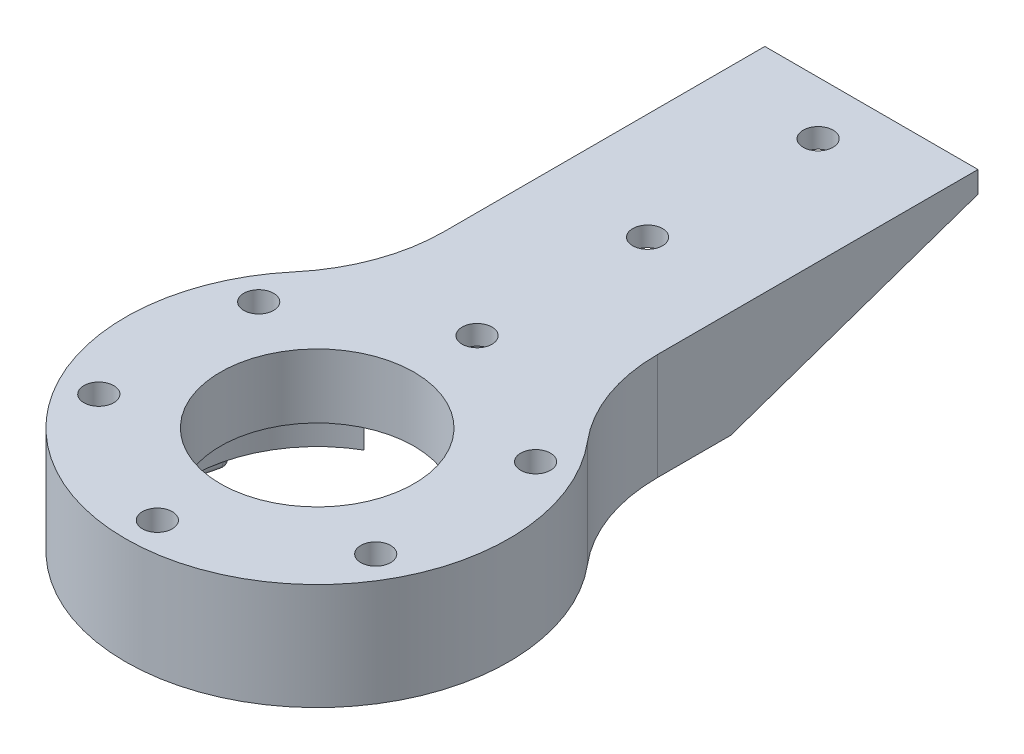
SolidWorks part; units mm, degrees
ref_plane "Front Plane" through (0, 0, 0) normal (0, 0, 1) x (1, 0, 0)
ref_plane "Top Plane" through (0, 0, 0) normal (0, 1, 0) x (1, 0, 0)
ref_plane "Right Plane" through (0, 0, 0) normal (1, 0, 0) x (0, 0, -1)
sketch "Sketch1" plane through (0, 0, 0) normal (0, 1, 0) x (1, 0, 0)
  line L0 (0, 82.55) -> (0, 0) construction
  line L1 (-15.875, 82.55) -> (15.875, 82.55)
  line L2 (-15.875, 82.55) -> (-15.875, 23.7595)
  line L4 (15.875, 82.55) -> (15.875, 23.7595)
  circle A0 centre (0, 0) radius 23.8125 construction
  arc A1 (-15.875, 23.7595) -> (15.875, 23.7595) centre (0, 0) ccw
  circle A2 centre (0, 0) radius 14.4145
  circle A3 centre (0, 23.8125) radius 2.2225
  circle A4 centre (20.6222, 11.9062) radius 2.2225
  circle A5 centre (20.6222, -11.9062) radius 2.2225
  circle A6 centre (0, -23.8125) radius 2.2225
  circle A7 centre (-20.6222, -11.9063) radius 2.2225
  circle A8 centre (-20.6222, 11.9063) radius 2.2225
  circle A9 centre (0, 49.2125) radius 2.2225
  circle A10 centre (0, 74.6125) radius 2.2225
  point P4 (0, 82.55)
  point P25 (0, 0)
  dimension "D1" = 47.625
  dimension "D2" = 82.55
  dimension "D4" = 28.575
  dimension "D5" = 28.829
  dimension "D6" = 4.445
  dimension "D8" = 3
  dimension "D3" = 31.75
  dimension "D7" = 6
extrude "Boss-Extrude1" add sketch "Sketch1" along normal blind 15.875
fillet "Fillet1" radius 25.4 2 edges at (-15.875, 7.9375, -23.7595) (15.875, 7.9375, -23.7595)
sketch "Sketch2" plane through (0, 0, -82.55) normal (0, 0, -1) x (-1, 0, 0)
  line L1 (12.8905, -12.954) -> (-12.8905, -12.954)
  line L2 (12.8905, -12.954) -> (12.8905, 12.954)
  line L3 (12.8905, 12.954) -> (-12.8905, 12.954)
  line L4 (-12.8905, -12.954) -> (-12.8905, 12.954)
  line L5 (12.8905, -12.954) -> (-12.8905, 12.954) construction
  line L6 (12.8905, 12.954) -> (-12.8905, -12.954) construction
  line L7 (-15.875, 0) -> (15.875, 0) construction
  point P0 (0, 0)
  dimension "D1" = 25.781
  dimension "D2" = 25.908
extrude "Cut-Extrude1" cut sketch "Sketch2" against normal blind 66.04
chamfer "Chamfer1" distance 36.83 angle 19 2 edges at (14.3827, 0, -82.55) (-14.3827, 0, -82.55) first distance on face at (0, 0, -42.1562)
sketch "Sketch3" plane through (0, 0, 0) normal (0, -1, 0) x (1, 0, 0)
  circle A0 centre (0, 0) radius 19.05
  dimension "D1" = 38.1
extrude "Cut-Extrude2" cut sketch "Sketch3" against normal offset from surface (6.3246 mm away) 9.5504 up to face at (0, 15.875, -46.99)
sketch "Sketch4" plane through (0, 0, 0) normal (0, -1, 0) x (1, 0, 0)
  line L0 (3.8088, 21.601) -> (4.4493, 25.2333)
  line L1 (16.8026, 14.0991) -> (19.628, 16.4699)
  line L2 (0, 0) -> (0, 23.9187) construction
  line L3 (0, 0) -> (20.6222, 11.9062) construction
  line L4 (20.6115, 7.502) -> (24.0773, 8.7634)
  line L5 (20.6115, -7.502) -> (24.0773, -8.7634)
  line L6 (16.8026, -14.0991) -> (19.628, -16.4699) construction
  line L7 (3.8088, -21.601) -> (4.4493, -25.2333) construction
  line L8 (-3.8088, -21.601) -> (-4.4493, -25.2333) construction
  line L9 (-16.8026, -14.0991) -> (-19.628, -16.4699) construction
  line L10 (-20.6115, -7.502) -> (-24.0773, -8.7634) construction
  line L11 (-20.6115, 7.502) -> (-24.0773, 8.7634) construction
  line L12 (-16.8026, 14.0991) -> (-19.628, 16.4699) construction
  line L13 (-3.8088, 21.601) -> (-4.4493, 25.2333) construction
  line L14 (-20.6983, -7.2633) -> (-24.1642, -8.5247)
  line L15 (-20.6983, 7.2633) -> (-24.1642, 8.5247)
  line L16 (-16.6394, 14.2936) -> (-19.4647, 16.6644)
  line L17 (-4.059, 21.5569) -> (-4.6994, 25.1892)
  arc A6 (9.5038, -16.51) -> (-9.5038, -16.51) centre (0, 0) ccw construction
  arc A8 (9.5038, -16.51) -> (-9.5038, -16.51) centre (0, 0) ccw construction
  arc A9 (20.5889, -17.3493) -> (-20.5889, -17.3493) centre (0, 0) ccw
  arc A10 (19.7429, 18.3062) -> (5.9822, 26.251) centre (0, 0) ccw
  arc A11 (15.0622, 14.2007) -> (4.7671, 20.1446) centre (0, 0) ccw
  arc A12 (19.7429, 18.3062) -> (19.628, 16.4699) centre (18.8117, 17.4427) cw
  arc A13 (16.8026, 14.0991) -> (15.0622, 14.2007) centre (15.9863, 15.0719) cw
  arc A14 (4.7671, 20.1446) -> (3.8088, 21.601) centre (5.0596, 21.3805) cw
  arc A15 (5.9822, 26.251) -> (4.4493, 25.2333) centre (5.7, 25.0127) ccw
  arc A16 (19.8293, 5.9439) -> (20.6115, 7.502) centre (21.0458, 6.3086) cw
  arc A17 (25.7251, -7.9448) -> (25.7251, 7.9448) centre (0, 0) ccw
  arc A18 (25.7251, 7.9448) -> (24.0773, 8.7634) centre (24.5117, 7.57) ccw
  arc A19 (25.7251, -7.9448) -> (24.0773, -8.7634) centre (24.5117, -7.57) cw
  arc A20 (20.6115, -7.502) -> (19.8293, -5.9439) centre (21.0458, -6.3086) cw
  arc A21 (19.8293, -5.9439) -> (19.8293, 5.9439) centre (0, 0) ccw
  arc A22 (15.0622, -14.2007) -> (16.8026, -14.0991) centre (15.9863, -15.0719) cw construction
  arc A23 (5.9822, -26.251) -> (19.7429, -18.3062) centre (0, 0) ccw construction
  arc A24 (19.7429, -18.3062) -> (19.628, -16.4699) centre (18.8117, -17.4427) ccw construction
  arc A25 (5.9822, -26.251) -> (4.4493, -25.2333) centre (5.7, -25.0127) cw construction
  arc A26 (3.8088, -21.601) -> (4.7671, -20.1446) centre (5.0596, -21.3805) cw construction
  arc A27 (4.7671, -20.1446) -> (15.0622, -14.2007) centre (0, 0) ccw construction
  arc A28 (-4.7671, -20.1446) -> (-3.8088, -21.601) centre (-5.0596, -21.3805) cw construction
  arc A29 (-19.7429, -18.3062) -> (-5.9822, -26.251) centre (0, 0) ccw construction
  arc A30 (-5.9822, -26.251) -> (-4.4493, -25.2333) centre (-5.7, -25.0127) ccw construction
  arc A31 (-19.7429, -18.3062) -> (-19.628, -16.4699) centre (-18.8117, -17.4427) cw construction
  arc A32 (-16.8026, -14.0991) -> (-15.0622, -14.2007) centre (-15.9863, -15.0719) cw construction
  arc A33 (-15.0622, -14.2007) -> (-4.7671, -20.1446) centre (0, 0) ccw construction
  arc A34 (-19.8293, -5.9439) -> (-20.6115, -7.502) centre (-21.0458, -6.3086) cw construction
  arc A35 (-25.7251, 7.9448) -> (-25.7251, -7.9448) centre (0, 0) ccw construction
  arc A36 (-25.7251, -7.9448) -> (-24.0773, -8.7634) centre (-24.5117, -7.57) ccw construction
  arc A37 (-25.7251, 7.9448) -> (-24.0773, 8.7634) centre (-24.5117, 7.57) cw construction
  arc A38 (-20.6115, 7.502) -> (-19.8293, 5.9439) centre (-21.0458, 6.3086) cw construction
  arc A39 (-19.8293, 5.9439) -> (-19.8293, -5.9439) centre (0, 0) ccw construction
  arc A40 (-15.0622, 14.2007) -> (-16.8026, 14.0991) centre (-15.9863, 15.0719) cw construction
  arc A41 (-5.9822, 26.251) -> (-19.7429, 18.3062) centre (0, 0) ccw construction
  arc A42 (-19.7429, 18.3062) -> (-19.628, 16.4699) centre (-18.8117, 17.4427) ccw construction
  arc A43 (-5.9822, 26.251) -> (-4.4493, 25.2333) centre (-5.7, 25.0127) cw construction
  arc A44 (-3.8088, 21.601) -> (-4.7671, 20.1446) centre (-5.0596, 21.3805) cw construction
  arc A45 (-4.7671, 20.1446) -> (-15.0622, 14.2007) centre (0, 0) ccw construction
  arc A46 (-25.4824, -7.8698) -> (-24.1642, -8.5247) centre (-24.5117, -7.57) ccw
  arc A47 (-25.4824, 7.8698) -> (-25.4824, -7.8698) centre (0, 0) ccw
  arc A48 (-25.4824, 7.8698) -> (-24.1642, 8.5247) centre (-24.5117, 7.57) cw
  arc A49 (-20.6983, 7.2633) -> (-20.0726, 6.0168) centre (-21.0458, 6.3086) cw
  arc A50 (-20.0726, 6.0168) -> (-20.0726, -6.0168) centre (0, 0) ccw
  arc A51 (-20.0726, -6.0168) -> (-20.6983, -7.2633) centre (-21.0458, -6.3086) cw
  arc A52 (-19.5567, 18.1335) -> (-19.4647, 16.6644) centre (-18.8117, 17.4427) ccw
  arc A53 (-5.9258, 26.0034) -> (-19.5567, 18.1335) centre (0, 0) ccw
  arc A54 (-5.9258, 26.0034) -> (-4.6994, 25.1892) centre (-5.7, 25.0127) cw
  arc A55 (-4.059, 21.5569) -> (-4.8256, 20.3918) centre (-5.0596, 21.3805) cw
  arc A56 (-4.8256, 20.3918) -> (-15.247, 14.375) centre (0, 0) ccw
  arc A57 (-15.247, 14.375) -> (-16.6394, 14.2936) centre (-15.9863, 15.0719) cw
  point P88 (0, 0)
  dimension "D1" = 1.651
  dimension "D5" = 1.27
  dimension "D3" = 10
  dimension "D4" = 10
  dimension "D2" = 1.651
  dimension "D7" = 0.254
  dimension "D8" = 0.254
  dimension "D6" = 6
extrude "Boss-Extrude2" add sketch "Sketch4" along normal blind 2.921 contours A57 A56 A55 L17 A54 A53 A52 L16 | A51 A50 A49 L15 A48 A47 A46 L14 region at (-23.4831, 0, 0) region at (-11.7416, 0, 20.337)
extrude "Cut-Extrude3" cut sketch "Sketch4<3>" against normal blind 3.175 contours A10 A15 L0 A14 A11 A13 L1 A12 | A21 A20 L5 A19 A17 A18 L4 A16 region at (23.4752, 0, 0) region at (11.7376, 0, 20.3301)
sketch "Sketch4<3>" plane through (0, 0, 0) normal (0, -1, 0) x (1, 0, 0) same geometry as "Sketch4"
fillet "Fillet2" radius 1.27 16 edges at (-22.4313, -2.921, -7.894) (-24.9637, -2.921, -8.4799) (-26.67, -2.921, 0) (-24.9637, -2.921, 8.4799) (-22.4313, -2.921, 7.894) (-20.1378, -2.921, 6.7644) (-20.955, -2.921, 0) (-20.1378, -2.921, -6.7644) (-18.052, -2.921, 15.479) (-19.8257, -2.921, 17.3793) (-13.335, -2.921, 23.0969) (-5.138, -2.921, 25.8592) (-4.3792, -2.921, 23.3731) (-4.2108, -2.921, 20.8221) (-10.4775, -2.921, 18.1476) (-15.927, -2.921, 14.0577)
sketch "Sketch6" [suppressed] plane through (0, 19.05, 0) normal (0, 1, 0) x (1, 0, 0)
  line L3 (-15.875, 82.55) -> (-15.875, 34.7804)
  line L4 (15.875, 34.7804) -> (15.875, 82.55)
  line L5 (15.875, 82.55) -> (-15.875, 82.55)
  line L6 (-15.875, 82.55) -> (-15.875, 34.7804)
  line L7 (15.875, 34.7804) -> (15.875, 82.55)
  line L8 (15.875, 82.55) -> (-15.875, 82.55)
  circle A0 centre (0, 0) radius 14.4145 construction
  circle A1 centre (0, 0) radius 14.4145
  arc A3 (-21.8515, 18.4131) -> (-15.875, 34.7804) centre (-41.275, 34.7804) ccw
  arc A4 (-21.8515, 18.4131) -> (21.8515, 18.4131) centre (0, 0) ccw
  arc A5 (15.875, 34.7804) -> (21.8515, 18.4131) centre (41.275, 34.7804) ccw
  arc A6 (-21.8515, 18.4131) -> (-15.875, 34.7804) centre (-41.275, 34.7804) ccw
  arc A7 (-21.8515, 18.4131) -> (21.8515, 18.4131) centre (0, 0) ccw
  arc A8 (15.875, 34.7804) -> (21.8515, 18.4131) centre (41.275, 34.7804) ccw
  dimension "D1" = 0
extrude "Boss-Extrude3" [suppressed] add sketch "Sketch6" along normal blind 1.27
sketch "Sketch8" [suppressed] plane through (0, 19.05, 0) normal (0, -1, 0) x (1, 0, 0)
  line L1 (2.361, -19.7231) -> (-2.361, -19.7231)
  line L2 (-2.361, -19.7231) -> (-4.722, -23.8125)
  line L3 (-4.722, -23.8125) -> (-2.361, -27.9019)
  line L4 (-2.361, -27.9019) -> (2.361, -27.9019)
  line L5 (2.361, -27.9019) -> (4.722, -23.8125)
  line L6 (4.722, -23.8125) -> (2.361, -19.7231)
  circle A0 centre (0, -23.8125) radius 4.0894 construction
  dimension "D1" = 8.1788
extrude "Cut-Extrude4" [suppressed] cut sketch "Sketch8" against normal through all and the other way blind 2.54
pattern_circular "CirPattern1" [suppressed] count 6 over 360 of bodies 107
pattern_linear "LPattern1" [suppressed] count 3 spacing 25.4 of bodies 108
